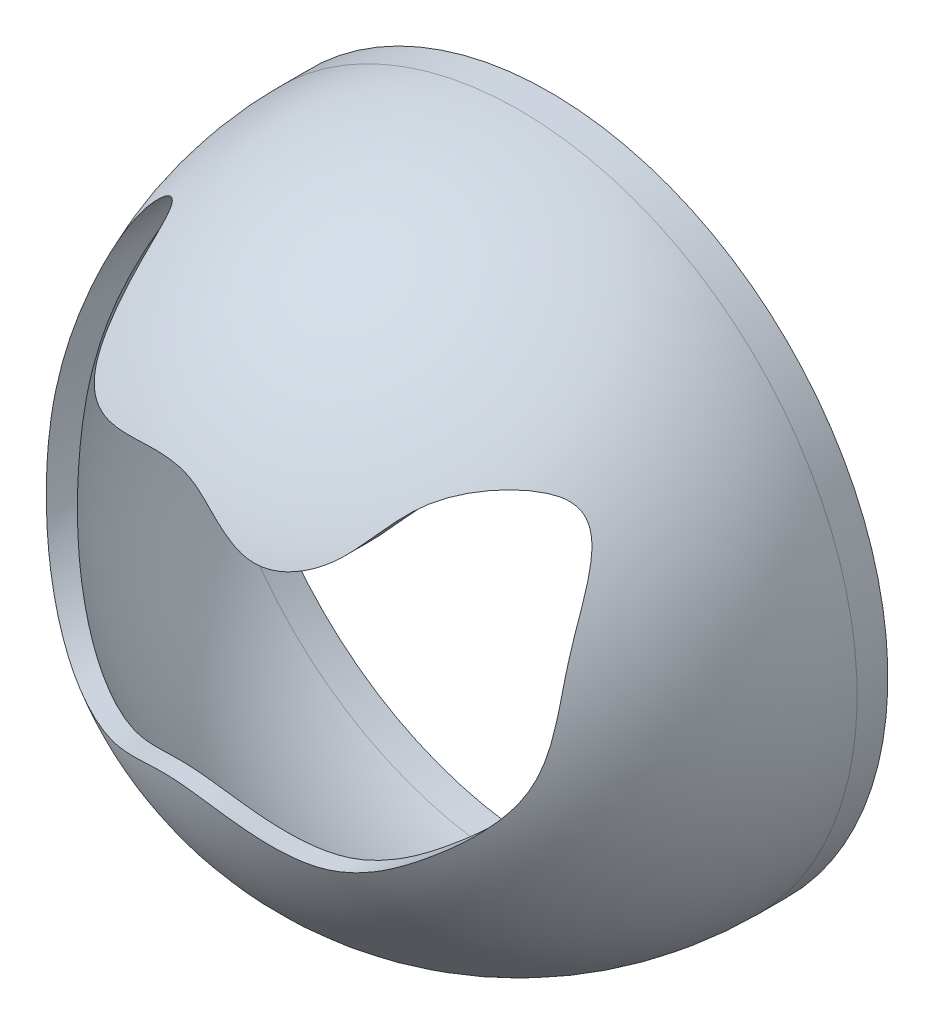
SolidWorks part; units mm, degrees
ref_plane "Front Plane" through (0, 0, 0) normal (0, 0, 1) x (1, 0, 0)
ref_plane "Top Plane" through (0, 0, 0) normal (0, 1, 0) x (1, 0, 0)
ref_plane "Right Plane" through (0, 0, 0) normal (1, 0, 0) x (0, 0, -1)
sketch "Sketch2" plane through (0, 0, 0) normal (1, 0, 0) x (0, 0, -1)
  line L7 (90.5803, 0) -> (147.5803, 0)
  line L8 (147.5803, 0) -> (147.5803, 52)
  line L9 (147.5803, 52) -> (142.5803, 52)
  line L10 (142.5803, 52) -> (142.5803, 0) construction
  line L11 (90.5803, 0) -> (46.7658, 0) construction
  arc A1 (142.5803, 52) -> (90.5803, 0) centre (142.5803, 0) ccw
  dimension "D4" = 52
  dimension "D3" = 5
revolve "Revolve1" add sketch "Sketch2" angle 360 about L11
shell "Shell1" thickness 3 removed face at (-52, 0, -147.5803) outward yes
sketch "Sketch5" plane through (0, 0, 0) normal (0, 1, 0) x (1, 0, 0)
  line L0 (-55, 147.5803) -> (55, 147.5803) construction
  line L1 (55, 147.5803) -> (-55, 147.5803) construction
  line L2 (0, 147.5803) -> (0, 100.0199) construction
  line L4 (-32, 147.5803) -> (32, 147.5803)
  line L5 (-32, 147.5803) -> (-32, 106.5803)
  line L6 (-32, 106.5803) -> (32, 106.5803)
  line L7 (32, 147.5803) -> (32, 106.5803)
  point P12 (0, 147.5803)
  dimension "D1" = 64
  dimension "D2" = 41
ref_plane "Plane1" through (0, 0, -67.5803) normal (0, 0, -1) x (-1, 0, 0)
ref_plane "Plane2" through (0, 0, -147.5803) normal (0, 0, 1) x (1, 0, 0)
ref_plane "Plane3" through (0, 0, -147.5803) normal (0, 0, -1) x (-1, 0, 0)
sketch "Sketch9" plane through (0, 0, -67.5803) normal (0, 0, -1) x (-1, 0, 0)
  line L0 (-55.6458, -11.9943) -> (52.3542, -11.9943) construction
  spline S0 degree 3 poles (44.8161, 28.0236) (28.7277, 42.6743) (32.54, 20.2387) (15.8788, 24.1621) (4.2119, 27.0484) (-6.5106, 18.0686) (-18.3342, 22.6851) (-23.1434, 32.6857) (-39.6569, 33.7699) (-41.598, 14.1347) (-41.9669, -2.745) (-29.8368, -13.8632) (-17.2043, -21.4083) (-6.0413, -16.0953) (5.6294, -13.1484) (17.3221, -19.5249) (33.3647, -17.5828) (45.6329, -4.5882) (45.83, 14.0305) (44.8161, 28.0236) (28.7277, 42.6743) (32.54, 20.2387) knots -0.180304 -0.109918 -0.040571 0 0.051097 0.09419 0.148468 0.194376 0.235839 0.274592 0.317068 0.383104 0.457294 0.510351 0.565253 0.613192 0.644405 0.701513 0.757417 0.819696 0.890082 0.959429 1 1.051097 1.09419 1.148468 only from (32.0815, 37.0933) to (32.0815, 37.0933)
extrude "Cut-Extrude1" cut sketch "Sketch9" along normal blind 70
